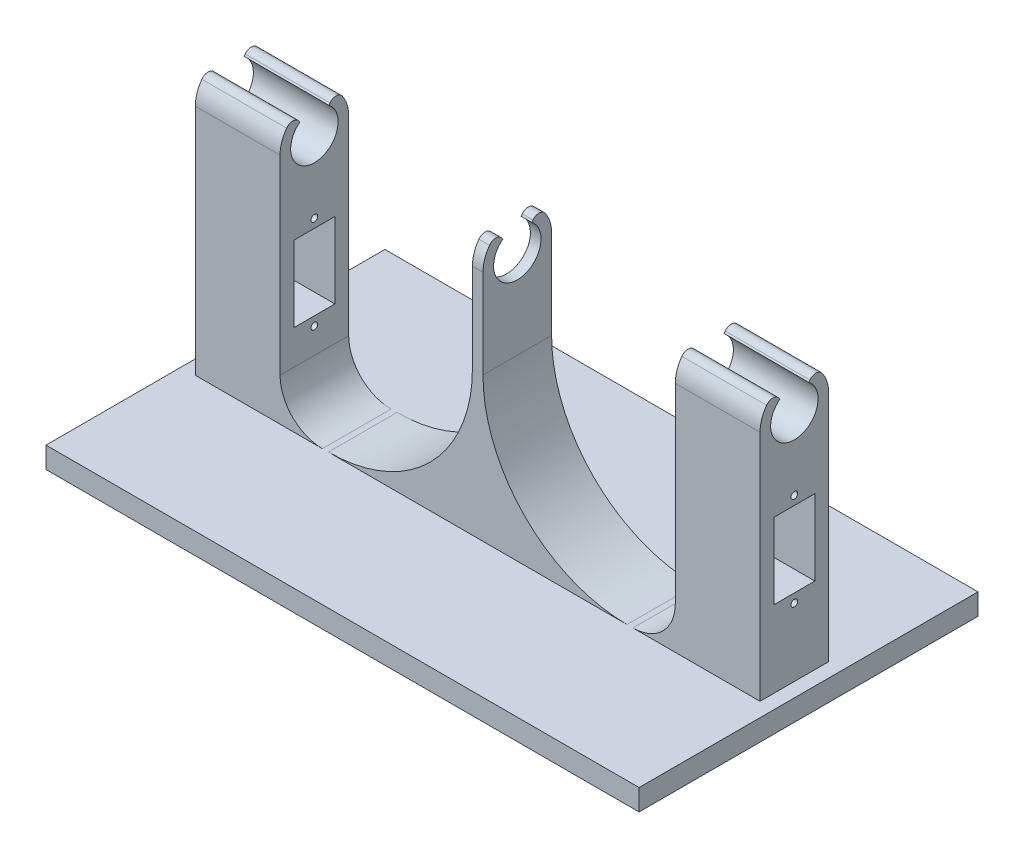
SolidWorks part; units mm, degrees
ref_plane "Front Plane" through (0, 0, 0) normal (0, 0, 1) x (1, 0, 0)
ref_plane "Top Plane" through (0, 0, 0) normal (0, 1, 0) x (1, 0, 0)
ref_plane "Right Plane" through (0, 0, 0) normal (1, 0, 0) x (0, 0, -1)
sketch "Sketch1" plane through (0, 0, 0) normal (0, 1, 0) x (1, 0, 0)
  line L1 (-88.9, -50.8) -> (88.9, -50.8)
  line L2 (-88.9, -50.8) -> (-88.9, 50.8)
  line L3 (-88.9, 50.8) -> (88.9, 50.8)
  line L4 (88.9, -50.8) -> (88.9, 50.8)
  line L5 (-88.9, -50.8) -> (88.9, 50.8) construction
  line L6 (-88.9, 50.8) -> (88.9, -50.8) construction
  point P0 (0, 0)
  dimension "D1" = 177.8
  dimension "D2" = 101.6
extrude "Boss-Extrude1" add sketch "Sketch1" along normal blind 6.35
sketch "Sketch2" plane through (-88.9, 0, 0) normal (-1, 0, 0) x (0, 0, 1)
  line L0 (-50.8, 0) -> (50.8, 0) construction
  line L1 (-10.287, 0) -> (10.287, 0)
  line L2 (-10.287, 0) -> (-10.287, 76.2)
  line L4 (10.287, 0) -> (10.287, 76.2)
  line L5 (0, 76.2) -> (0, 0) construction
  line L6 (0, 76.2) -> (6.2623, 84.3612)
  line L7 (0, 76.2) -> (-6.2623, 84.3612)
  arc A1 (10.287, 76.2) -> (6.2623, 84.3612) centre (0, 76.2) ccw
  arc A2 (-4.3295, 81.8423) -> (4.3295, 81.8423) centre (0, 76.2) ccw
  arc A3 (-6.2623, 84.3612) -> (-10.287, 76.2) centre (0, 76.2) ccw
  point P9 (0, 0)
  line M8 (50.8, 6.35) -> (-50.8, 6.35)
  dimension "D2" = 3.175
  dimension "D3" = 14.224
  dimension "D1" = 76.2
  dimension "D4" = 75
extrude "Boss-Extrude2" add sketch "Sketch2" against normal up to surface (177.8 mm away) contours A2 L5 L4 A1 L6 M8 | L5 A2 L7 A3 L2 M8 region at (-88.9, 40.8652, -5.3523) region at (-88.9, 40.8652, 5.3523) up to face at (88.9, 3.175, 0)
sketch "Sketch3" plane through (0, 6.35, 0) normal (0, 1, 0) x (1, 0, 0)
  line L0 (-1.5875, 50.8) -> (-1.5875, -50.8)
  line L1 (88.9, 50.8) -> (-88.9, 50.8) construction
  line L2 (-88.9, -50.8) -> (88.9, -50.8) construction
  line L3 (1.5875, 50.8) -> (1.5875, -50.8)
  line L4 (59.2455, 50.8) -> (59.2455, -50.8)
  line L5 (84.6455, 50.8) -> (84.6455, -50.8)
  line L6 (-1.5875, 50.8) -> (1.5875, 50.8) construction
  line L7 (0, 50.8) -> (0, 0) construction
  line L8 (1.5875, -50.8) -> (59.2455, -50.8)
  line L9 (1.5875, 50.8) -> (59.2455, 50.8)
  line L10 (84.6455, 50.8) -> (88.9, 50.8)
  line L11 (88.9, 50.8) -> (88.9, -50.8)
  line L12 (88.9, -50.8) -> (84.6455, -50.8)
  line L13 (-84.6455, -50.8) -> (-84.6455, 50.8)
  line L14 (-84.6455, 50.8) -> (-88.9, 50.8)
  line L15 (-88.9, 50.8) -> (-88.9, -50.8)
  line L16 (-88.9, -50.8) -> (-84.6455, -50.8)
  line L17 (-59.2455, 50.8) -> (-59.2455, -50.8)
  line L18 (-59.2455, -50.8) -> (-1.5875, -50.8)
  line L19 (-1.5875, 50.8) -> (-59.2455, 50.8)
  dimension "D1" = 3.175
  dimension "D2" = 25.4
  dimension "D3" = 25.4
  dimension "D4" = 57.658
  dimension "D5" = 57.658
extrude "Cut-Extrude1" cut sketch "Sketch3" along normal through all from surface starting at face at (0, 6.35, -30.5435)
fillet "Fillet1" radius 43.18 2 edges at (1.5875, 6.35, 0) (-1.5875, 6.35, 0)
fillet "Fillet2" radius 12.7 2 edges at (59.2455, 6.35, 0) (-59.2455, 6.35, 0)
fillet "Fillet3" radius 2.286 6 edges at (71.9455, 84.3612, 6.2623) (71.9455, 84.3612, -6.2623) (0, 84.3612, 6.2623) (0, 84.3612, -6.2623) (-71.9455, 84.3612, 6.2623) (-71.9455, 84.3612, -6.2623)
sketch "Sketch5" plane through (59.2455, 0, 0) normal (-1, 0, 0) x (0, 0, 1)
  line L0 (0, 76.2) -> (0, 52.05) construction
  line L1 (-6.15, 52.05) -> (6.15, 52.05)
  line L2 (-6.15, 52.05) -> (-6.15, 29.35)
  line L3 (-6.15, 29.35) -> (6.15, 29.35)
  line L4 (6.15, 52.05) -> (6.15, 29.35)
  circle A0 centre (0, 54.7) radius 1
  circle A1 centre (0, 26.7) radius 1
  point P7 (0, 45.95)
  point P12 (0, 0)
  point P13 (0, 0)
  dimension "D7" = 2
  dimension "D8" = 2
  dimension "D1" = 12.3
  dimension "D2" = 22.7
  dimension "D3" = 6.1
  dimension "D4" = 30.25
  dimension "D5" = 2.65
  dimension "D6" = 2.65
extrude "Cut-Extrude2" cut sketch "Sketch5" against normal through all
extrude "Cut-Extrude3" cut sketch "Sketch5<2>" along normal through all from surface starting at face at (-59.2455, 67.2608, 0)
sketch "Sketch5<2>" plane through (59.2455, 0, 0) normal (-1, 0, 0) x (0, 0, 1) same geometry as "Sketch5"
